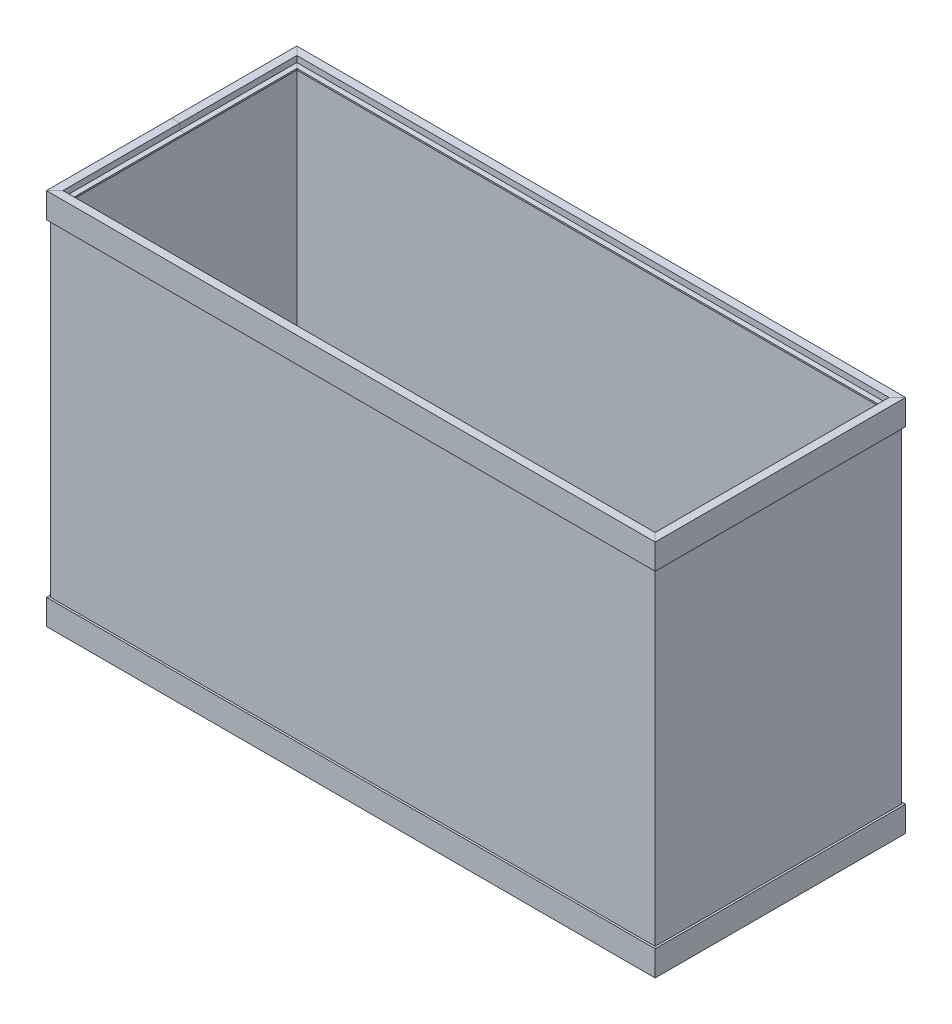
SolidWorks part; units mm, degrees
ref_plane "Front Plane" through (0, 0, 0) normal (0, 0, 1) x (1, 0, 0)
ref_plane "Top Plane" through (0, 0, 0) normal (0, 1, 0) x (1, 0, 0)
ref_plane "Right Plane" through (0, 0, 0) normal (1, 0, 0) x (0, 0, -1)
sketch "Sketch1" plane through (0, 0, 0) normal (0, 1, 0) x (1, 0, 0)
  line L0 (-379, -154.4) -> (-379, 154.4)
  line L1 (-375, -150.4) -> (375, -150.4)
  line L2 (-375, -150.4) -> (-375, 150.4)
  line L3 (-375, 150.4) -> (375, 150.4)
  line L4 (375, -150.4) -> (375, 150.4)
  line L5 (-375, -150.4) -> (375, 150.4) construction
  line L6 (-375, 150.4) -> (375, -150.4) construction
  line L7 (-379, 154.4) -> (379, 154.4)
  line L8 (379, -154.4) -> (379, 154.4)
  line L9 (-379, -154.4) -> (379, -154.4)
  point P0 (0, 0)
  dimension "D1" = 750
  dimension "D2" = 300.8
  dimension "D3" = 4
extrude "Tank Walls" add sketch "Sketch1" along normal blind 461.2
extrude "Tank Floor" add sketch "Sketch1<2>" along normal blind 4 contours L1 L4 L3 L2 | L0 L9 L8 L7 L4 L1 L2 L3 region at (-378.1815, 0, 0) region at (0, 0, 0)
sketch "Sketch1<2>" plane through (0, 0, 0) normal (0, 1, 0) x (1, 0, 0) same geometry as "Sketch1"
sketch "Sketch2" plane through (0, 0, 0) normal (0, 0, 1) x (1, 0, 0)
  line L0 (-379, 461.2) -> (-364.84, 461.2)
  line L1 (-364.84, 461.2) -> (-364.84, 463.105)
  line L2 (-364.84, 463.105) -> (-371.19, 463.105)
  line L3 (-371.19, 463.105) -> (-371.19, 470.725)
  line L4 (-371.19, 470.725) -> (-381.54, 470.725)
  line L5 (-381.54, 470.725) -> (-381.54, 438.975)
  line L6 (-381.54, 438.975) -> (-379, 438.975)
  line L7 (-379, 461.2) -> (-379, 0) construction
  line L8 (-379, 438.975) -> (-379, 461.2)
  line L9 (-379, 461.2) -> (379, 461.2) construction
  line L10 (-375, 461.2) -> (-375, 4) construction
  dimension "D1" = 31.75
  dimension "D2" = 9.525
  dimension "D3" = 2.54
  dimension "D4" = 10.16
  dimension "D5" = 7.62
  dimension "D6" = 6.35
sketch "Sketch3" plane through (0, 461.2, 0) normal (0, 1, 0) x (1, 0, 0)
  line L4 (-379, -154.4) -> (379, -154.4)
  line L5 (379, -154.4) -> (379, 154.4)
  line L6 (379, 154.4) -> (-379, 154.4)
  line L7 (-379, 154.4) -> (-379, -154.4)
  line L8 (-379, -154.4) -> (379, -154.4)
  line L9 (379, -154.4) -> (379, 154.4)
  line L10 (379, 154.4) -> (-379, 154.4)
  line L11 (-379, 154.4) -> (-379, -154.4)
  dimension "D1" = 0
sweep "Top Rim" add profiles "Sketch2" path "Sketch3"
sketch "Sketch4" plane through (0, 0, 0) normal (0, 0, 1) x (1, 0, 0)
  line L0 (-379, 0) -> (-379, 29.21)
  line L1 (-379, 461.2) -> (-379, 0) construction
  line L2 (-379, 29.21) -> (-381.54, 29.21)
  line L3 (-381.54, 29.21) -> (-381.54, -2.54)
  line L4 (-381.54, -2.54) -> (-349.79, -2.54)
  line L5 (-349.79, -2.54) -> (-349.79, 0)
  line L6 (379, 0) -> (-379, 0) construction
  line L7 (-349.79, 0) -> (-379, 0)
  dimension "D1" = 31.75
  dimension "D2" = 31.75
  dimension "D3" = 2.54
  dimension "D4" = 2.54
sketch "Sketch5" plane through (0, 0, 0) normal (0, -1, 0) x (1, 0, 0)
  line L4 (379, 154.4) -> (-379, 154.4)
  line L5 (-379, 154.4) -> (-379, -154.4)
  line L6 (-379, -154.4) -> (379, -154.4)
  line L7 (379, -154.4) -> (379, 154.4)
  line L8 (379, 154.4) -> (-379, 154.4)
  line L9 (-379, 154.4) -> (-379, -154.4)
  line L10 (-379, -154.4) -> (379, -154.4)
  line L11 (379, -154.4) -> (379, 154.4)
  dimension "D1" = 0
sweep "Bottom Rim" add profiles "Sketch4" path "Sketch5"
